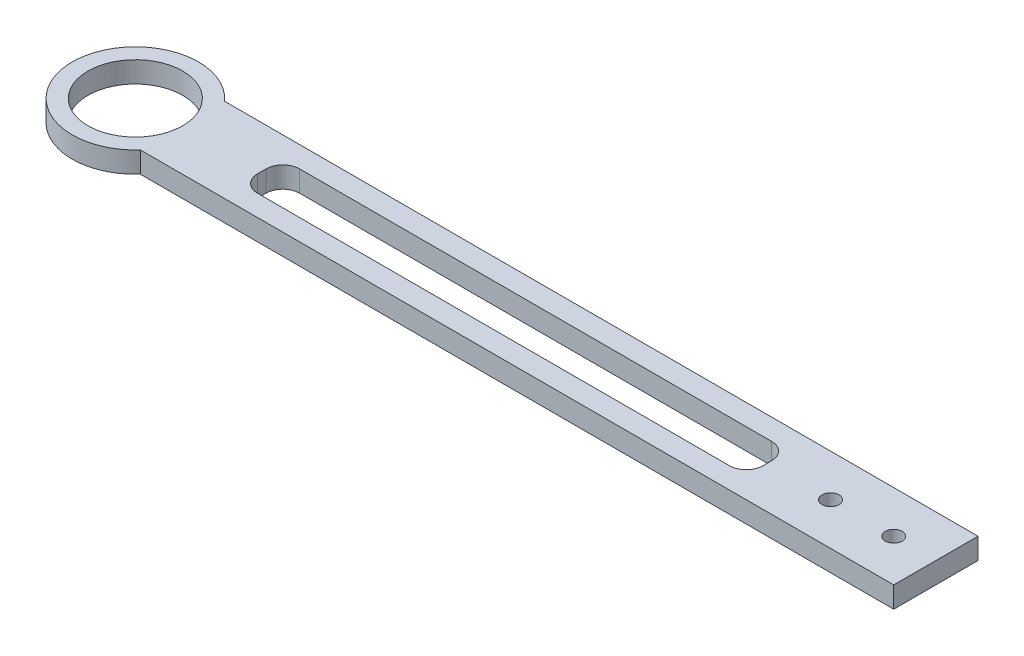
SolidWorks part; units mm, degrees
material "5052-O"
ref_plane "Front Plane" through (0, 0, 0) normal (0, 0, 1) x (1, 0, 0)
ref_plane "Top Plane" through (0, 0, 0) normal (0, 1, 0) x (1, 0, 0)
ref_plane "Right Plane" through (0, 0, 0) normal (1, 0, 0) x (0, 0, -1)
sketch "Sketch1" plane through (0, 0, 0) normal (0, 1, 0) x (1, 0, 0)
  line L1 (-127, -12.7) -> (127, -12.7)
  line L2 (-127, -12.7) -> (-127, 12.7)
  line L3 (-127, 12.7) -> (127, 12.7)
  line L4 (127, -12.7) -> (127, 12.7)
  line L5 (-127, -12.7) -> (127, 12.7) construction
  line L6 (-127, 12.7) -> (127, -12.7) construction
  point P0 (0, 0)
  dimension "D1" = 25.4
  dimension "D2" = 254
extrude "Boss-Extrude1" add sketch "Sketch1" along normal mid plane 6.35
fillet "Fillet1" radius 12.7 2 edges at (-127, 0, -12.7) (-127, 0, 12.7)
sketch "Sketch2" plane through (0, 3.175, 0) normal (0, 1, 0) x (1, 0, 0)
  line L0 (0, -36.7292) -> (0, 36.7292) construction
  line L1 (114.3, 0) -> (-114.3, 0) construction
  point P1 (95.25, 0)
  point P10 (0, 0)
  point P11 (0, 0)
  dimension "D1" = 12.7
  dimension "D2" = 19.05
hole_wizard "#10 Clearance Hole1" positions "Sketch5" profile "Sketch7" hole size "#10" standard "ANSI Inch" end condition through all
sketch "Sketch5" plane through (0, 3.175, 0) normal (0, 1, 0) x (1, 0, 0)
  point P0 (114.3, 0)
  point P3 (95.25, 0)
sketch "Sketch7" plane through (114.3, 3.175, 0) normal (1, 0, 0) x (0, 0, 1)
  line L0 (0, 0) -> (0, 6.35)
  line L1 (0, 6.35) -> (2.5527, 6.35)
  line L2 (2.5527, 6.35) -> (2.5527, 0)
  line L5 (2.5527, 0) -> (0, 0)
  line L11 (0, -6.35) -> (0, 107.95) construction
  dimension "Thru Hole Dia." = 5.1054
  dimension "Thru Hole Depth" = 6.35
sketch "Sketch9" plane through (0, 3.175, 0) normal (0, 1, 0) x (1, 0, 0)
  line L0 (127, 12.7) -> (-114.3, 12.7) construction
  line L1 (-76.2, -6.35) -> (76.2, -6.35)
  line L2 (-76.2, -6.35) -> (-76.2, 6.35)
  line L3 (-76.2, 6.35) -> (76.2, 6.35)
  line L4 (76.2, -6.35) -> (76.2, 6.35)
  line L5 (-76.2, -6.35) -> (76.2, 6.35) construction
  line L6 (-76.2, 6.35) -> (76.2, -6.35) construction
  point P0 (0, 0)
  dimension "D1" = 50.8
  dimension "D2" = 6.35
extrude "Cut-Extrude2" cut sketch "Sketch9" against normal through all
fillet "Fillet2" radius 5.08 4 edges at (-76.2, 0, -6.35) (-76.2, 0, 6.35) (76.2, 0, 6.35) (76.2, 0, -6.35)
sketch "Sketch11" plane through (0, -3.175, 0) normal (0, -1, 0) x (1, 0, 0)
  circle A0 centre (-114.3, 0) radius 19.05
  arc A1 (-114.3, 12.7) -> (-127, 0) centre (-114.3, 0) ccw construction
  dimension "D1" = 38.1
extrude "Boss-Extrude2" add sketch "Sketch11" against normal up to surface (6.35 mm away) up to face at (0, 3.175, 0)
sketch "Sketch10" plane through (0, -3.175, 0) normal (0, -1, 0) x (1, 0, 0)
  circle A0 centre (-114.3, 0) radius 14.2875
  arc A2 (-100.101, 12.7) -> (-100.101, -12.7) centre (-114.3, 0) ccw construction
  dimension "D1" = 28.575
extrude "Cut-Extrude3" cut sketch "Sketch10" against normal through all
